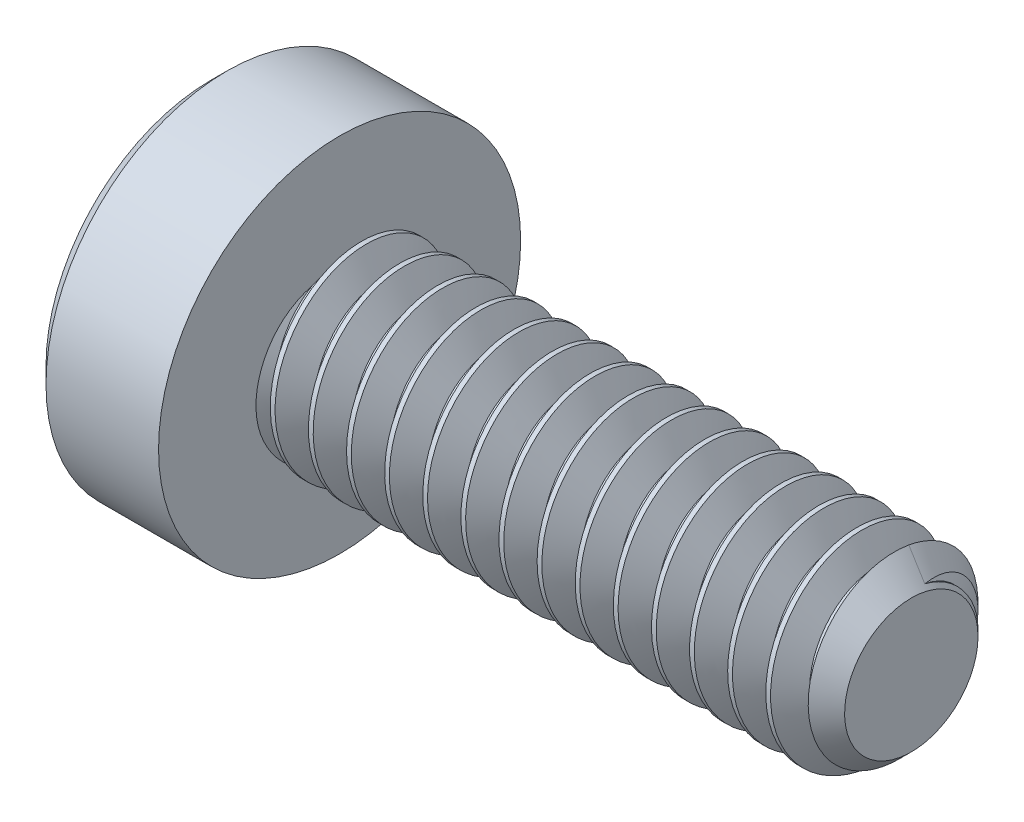
SolidWorks part; units mm, degrees
ref_plane "Front Plane" through (0, 0, 0) normal (0, 0, 1) x (1, 0, 0)
ref_plane "Top Plane" through (0, 0, 0) normal (0, 1, 0) x (1, 0, 0)
ref_plane "Right Plane" through (0, 0, 0) normal (1, 0, 0) x (0, 0, -1)
sketch "Sketch1" plane through (0, 0, 0) normal (0, 0, 1) x (1, 0, 0)
  line L0 (3, 0) -> (-3, 0) construction
  line L1 (3, 1) -> (3, -1) construction
  line L2 (-3, 1.9) -> (-3, -1.9) construction
  line L3 (-3, 1.9) -> (-4.1813, 1.9) construction
  line L4 (-4.1813, 1.9) -> (-4.35, 1.7312) construction
  line L5 (-4.35, 1.7312) -> (-4.35, -1.7313) construction
  line L6 (-4.35, -1.7313) -> (-4.1813, -1.9) construction
  line L7 (-4.1813, -1.9) -> (-3, -1.9) construction
  point P7 (-3.375, 0)
  point P12 (1.4, -1)
  dimension "D1" = 45
  dimension "D2" = 1.6
  dimension "Dec." = 2
  dimension "Length" = 6
  dimension "Head Dia" = 3.8
  dimension "Head Height" = 1.35
  dimension "Hex Depth" = 0.975
  dimension "Chamfer" = 0.1688
ref_plane "Plane1" through (3, 0, 0) normal (1, 0, 0) x (0, 0, -1)
ref_plane "Plane2" through (-4.35, 0, 0) normal (1, 0, 0) x (0, 0, -1)
sketch "Sketch2" plane through (3, 0, 0) normal (1, 0, 0) x (0, 0, -1)
  circle A0 centre (0, 0) radius 1
extrude "Boss-Extrude1" add sketch "Sketch2" against normal up to vertex (6 mm away) up to point (-3, 0, 0)
sketch "Sketch3" plane through (3, 0, 0) normal (1, 0, 0) x (0, 0, -1)
  circle A0 centre (0, 0) radius 1 construction
  circle A1 centre (0, 0) radius 1
curve "Helix/Spiral1" pitch 0.4 height 6.4 radius 1 centre (3, 0, 0) axis (-1, 0, 0) start towards (0, 1, 0) parameters "Pitch"=0.4
chamfer "Chamfer1" distance 0.3 angle 45 1 edges at (3, 0, -1)
sketch "Sketch5" plane through (0, 0, 0) normal (0, 0, 1) x (1, 0, 0)
  line L0 (2.825, 1) -> (3.175, 1)
  line L1 (3.175, 1) -> (3.025, 0.7402)
  line L2 (3.025, 0.7402) -> (2.975, 0.7402)
  line L3 (2.975, 0.7402) -> (2.825, 1)
  line L4 (3, 0.7402) -> (3, 1) construction
  line L5 (2.9, 0.8701) -> (3.1, 0.8701) construction
  dimension "D1" = 60
  dimension "D2" = 0.2
  dimension "D3" = 0.05
sweep "Cut-Sweep1" cut profiles "Sketch5" path "Helix/Spiral1"
sketch "Sketch4" plane through (-4.35, 0, 0) normal (1, 0, 0) x (0, 0, -1)
  line L0 (-1.9, 0.7937) -> (1.9, 0.7937) construction
  line L1 (0, 0.7506) -> (-0.65, 0.3753)
  line L2 (-0.65, 0.3753) -> (-0.65, -0.3753)
  line L3 (-0.65, -0.3753) -> (0, -0.7506)
  line L4 (0, -0.7506) -> (0.65, -0.3753)
  line L5 (0.65, -0.3753) -> (0.65, 0.3753)
  line L6 (0.65, 0.3753) -> (0, 0.7506)
  line L7 (0, 0) -> (0, 0.7937) construction
  circle A0 centre (0, 0) radius 0.65 construction
  dimension "D1" = 3.8
  dimension "Hex Size" = 1.3
  dimension "D2" = 0.7937
sketch "Sketch6" plane through (0, 0, 0) normal (0, 0, 1) x (1, 0, 0)
  line L0 (-4.1813, 1.9) -> (-4.35, 1.7312) construction
  line L1 (-3, 1.9) -> (-4.1813, 1.9) construction
  line L2 (-3, 1.9) -> (-3, -1.9) construction
  line L3 (-4.35, 1.7312) -> (-4.35, -1.7313) construction
  line L4 (-4.1813, 1.9) -> (-4.35, 1.7312)
  line L5 (-3, 1.9) -> (-4.1813, 1.9)
  line L6 (-3, 1.9) -> (-3, 0)
  line L7 (-4.35, 1.7312) -> (-4.35, 0)
  line L8 (-3, 0) -> (-4.35, 0) construction
  line L9 (-3, 0) -> (-4.35, 0)
revolve "Revolve1" add sketch "Sketch6" angle 360 about L8
extrude "Cut-Extrude1" cut sketch "Sketch4" along normal up to vertex (0.975 mm away) up to point (-3.375, 0, 0)
sketch "Sketch8" plane through (-4.35, 0, 0) normal (-1, 0, 0) x (0, 0, 1)
  circle A1 centre (0, 0) radius 0.7506
extrude "Cut-Extrude2" cut sketch "Sketch8" against normal through all draft 45
equation "\"D3@Helix/Spiral1\" = \"Length@Sketch1\"+\"Pitch@Helix/Spiral1\""
equation "\"D3@Sketch5\" = \"Pitch@Helix/Spiral1\"*.125"
equation "\"D2@Sketch5\" = \"Pitch@Helix/Spiral1\"*.50"
equation "\"D1@Chamfer1\" = \"Pitch@Helix/Spiral1\"*.75"
equation "\"D2@Sketch1\" = \"Pitch@Helix/Spiral1\"*4"
equation "\"D1@Sketch4\" = \"Head Dia@Sketch1\""
equation "\"Chamfer@Sketch1\" = \"Head Height@Sketch1\"/8"
